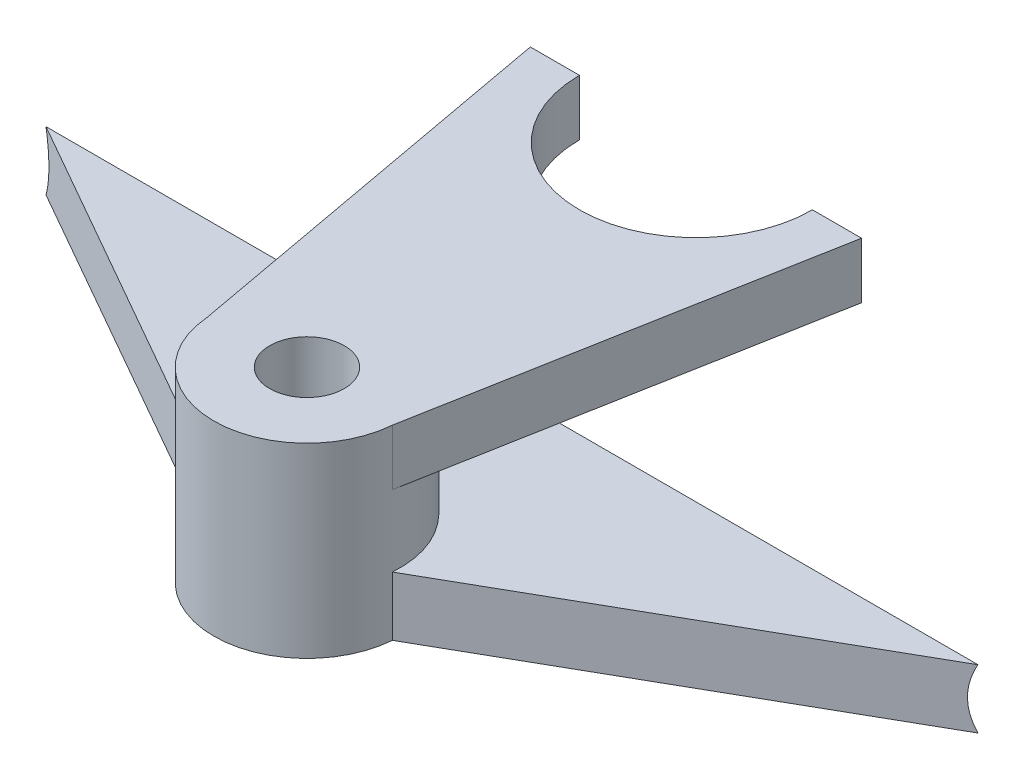
SolidWorks part; units mm, degrees
ref_plane "Front Plane" through (0, 0, 0) normal (0, 0, 1) x (1, 0, 0)
ref_plane "Top Plane" through (0, 0, 0) normal (0, 1, 0) x (1, 0, 0)
ref_plane "Right Plane" through (0, 0, 0) normal (1, 0, 0) x (0, 0, -1)
sketch "Sketch1" plane through (0, 0, 0) normal (0, 1, 0) x (1, 0, 0)
  line L0 (0, 0) -> (100, 0)
  line L4 (0, 0) -> (40.0326, -22.8063)
  line L5 (59.9674, -22.8063) -> (100, 0)
  line L6 (50, 0) -> (50, -17.1488) construction
  line L7 (40.0326, -22.8063) -> (59.9674, -22.8063) construction
  circle A0 centre (50, -22) radius 4
  circle A1 centre (50, -22) radius 10
  dimension "D2" = 20
  dimension "D3" = 8
  dimension "D1" = 100
  dimension "D4" = 22
extrude "Boss-Extrude1" add sketch "Sketch1" along normal blind 6.35 contours A1 L5 L0 L4 region at (50, 0, 7.514)
extrude "Boss-Extrude2" add sketch "Sketch1<3>" along normal blind 20 contours A1 A0 region at (49.6079, 0, 12.2908)
sketch "Sketch1<3>" plane through (0, 0, 0) normal (0, 1, 0) x (1, 0, 0) same geometry as "Sketch1"
ref_plane "Plane1" through (0, 10, 0) normal (0, 1, 0) x (1, 0, 0)
sketch "Sketch2" plane through (0, 0, 0) normal (1, 0, 0) x (0, 0, -1)
  line L0 (0, 3.175) -> (21.8325, 3.175) construction
  line L1 (0, 6.35) -> (0, 0) construction
  circle A0 centre (12.0901, 3.175) radius 12.5
  point P7 (12.089, 3.175)
  dimension "D1" = 25
extrude "Cut-Extrude1" cut sketch "Sketch2" along normal through all
sketch "Sketch3" plane through (0, 20, 0) normal (0, 1, 0) x (1, 0, 0)
  line L0 (50, 12.1937) -> (50, 19.7369) construction
  line L1 (40.0326, -22.8063) -> (59.9674, -22.8063)
  line L2 (40.0326, -22.8063) -> (40.0326, 12.1937)
  line L3 (40.0326, 12.1937) -> (59.9674, 12.1937)
  line L4 (59.9674, -22.8063) -> (59.9674, 12.1937)
  line L5 (67.77, 19.7369) -> (32.23, 19.7369)
  line L6 (50, 19.7369) -> (50, -18)
  line L7 (67.77, 19.7369) -> (59.9674, -22.8063)
  line L8 (32.23, 19.7369) -> (40.0326, -22.8063)
  circle A1 centre (50, -22) radius 4
  circle A2 centre (50, 19.7369) radius 12.5
  circle M8 centre (50, -22) radius 10
  dimension "D1" = 25
  dimension "D2" = 35
extrude "Boss-Extrude3" add sketch "Sketch3" against normal blind 6 contours A2 L2 L4 M8 | A2 L2 L6 M8 | A2 L5 L8 L2 M8 | A2 L4 L7 L5 M8 region at (37.2967, 20, -4.5993) region at (44.5908, 20, 2.7572) region at (62.7033, 20, -4.5993) region at (55.4092, 20, 2.7572)
